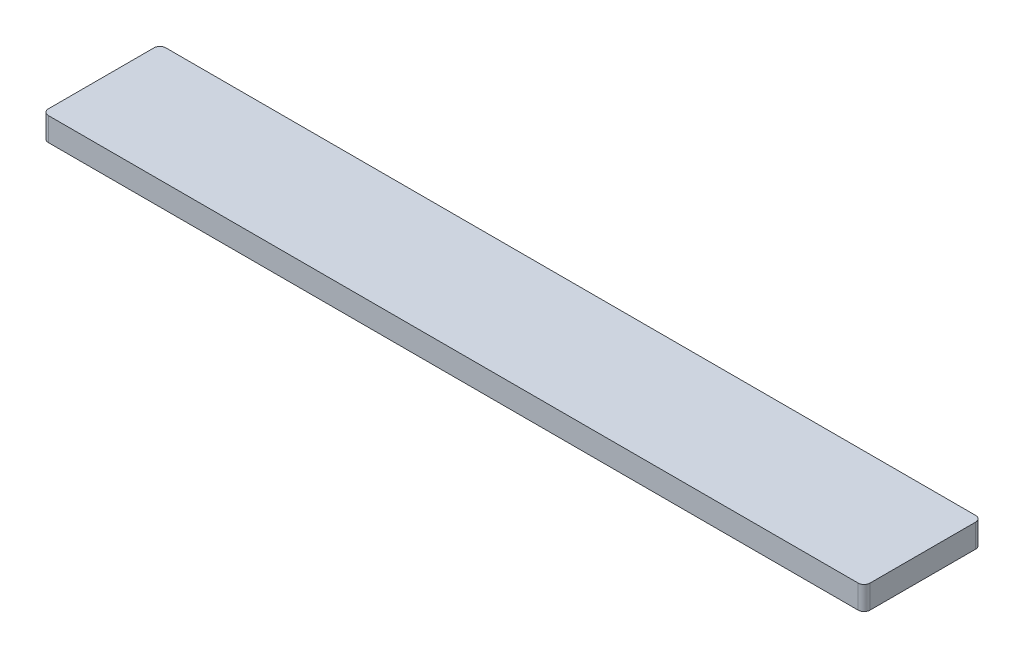
SolidWorks part; units mm, degrees
ref_plane "Front Plane" through (0, 0, 0) normal (0, 0, 1) x (1, 0, 0)
ref_plane "Top Plane" through (0, 0, 0) normal (0, 1, 0) x (1, 0, 0)
ref_plane "Right Plane" through (0, 0, 0) normal (1, 0, 0) x (0, 0, -1)
sketch "Sketch1" plane through (0, 0, 0) normal (0, 1, 0) x (1, 0, 0)
  line L0 (0, 0) -> (88.9, 0)
  line L1 (88.9, 0) -> (88.9, 12.7)
  line L2 (88.9, 12.7) -> (0, 12.7)
  line L3 (0, 12.7) -> (0, 0)
  dimension "D1" = 88.9
  dimension "D2" = 12.7
extrude "Boss-Extrude1" add sketch "Sketch1" along normal blind 2.54
fillet "Fillet1" radius 0.635 4 edges at (0, 1.27, -12.7) (88.9, 1.27, -12.7) (88.9, 1.27, 0) (0, 1.27, 0)
shell "Shell1" thickness 0.635 removed face at (44.45, 0, -6.35)
sketch "Sketch2" plane through (0, 1.905, 0) normal (0, -1, 0) x (-1, 0, 0)
  line L0 (-88.265, 6.35) -> (-0.635, 6.35) construction
  line L1 (-88.265, 0.635) -> (-88.265, 12.065) construction
  line L2 (-0.635, 12.065) -> (-0.635, 0.635) construction
  line L3 (-44.45, 12.065) -> (-44.45, 0.635) construction
  line L4 (-88.265, 12.065) -> (-0.635, 12.065) construction
  line L5 (-0.635, 0.635) -> (-88.265, 0.635) construction
  circle A0 centre (-69.85, 6.35) radius 2.54
  circle A1 centre (-19.05, 6.35) radius 2.54
  dimension "D1" = 5.08
  dimension "D2" = 5.08
  dimension "D3" = 25.4
  dimension "D4" = 25.4
extrude "Boss-Extrude2" add sketch "Sketch2" along normal blind 2.54
